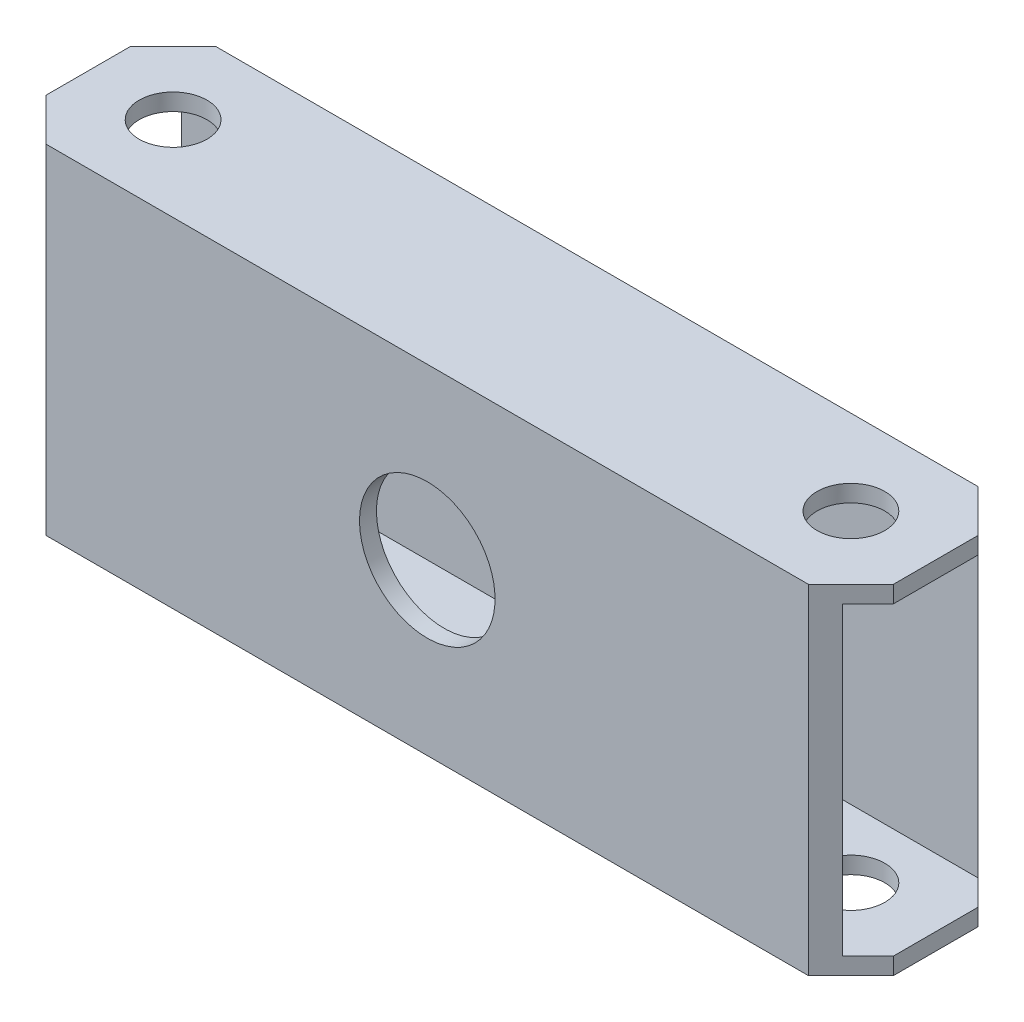
SolidWorks part; units mm, degrees
ref_plane "Front Plane" through (0, 0, 0) normal (0, 0, 1) x (1, 0, 0)
ref_plane "Top Plane" through (0, 0, 0) normal (0, 1, 0) x (1, 0, 0)
ref_plane "Right Plane" through (0, 0, 0) normal (1, 0, 0) x (0, 0, -1)
sketch "Sketch1" plane through (0, 0, 0) normal (0, 1, 0) x (1, 0, 0)
  line L1 (0, 0) -> (100, 0)
  line L2 (0, 0) -> (0, 20)
  line L3 (0, 20) -> (100, 20)
  line L4 (100, 0) -> (100, 20)
  dimension "D1" = 100
  dimension "D2" = 20
extrude "Boss-Extrude1" add sketch "Sketch1" along normal blind 40
sketch "Sketch2" plane through (0, 40, 0) normal (0, 1, 0) x (1, 0, 0)
  line L0 (50, 20) -> (50, 0)
  line L1 (100, 20) -> (0, 20) construction
  line L2 (0, 0) -> (100, 0) construction
  circle A0 centre (10, 10) radius 4
  circle A1 centre (90, 10) radius 4
extrude "Cut-Extrude1" cut sketch "Sketch2" against normal through all contours A0 | A1
sketch "Sketch3" plane through (0, 0, -20) normal (0, 0, -1) x (-1, 0, 0)
  line L0 (-100, 0) -> (0, 0) construction
  line L1 (0, 40) -> (0, 0) construction
  circle A0 centre (-50, 20) radius 8
  dimension "D1" = 16
  dimension "D2" = 20
  dimension "D3" = 50
extrude "Cut-Extrude2" cut sketch "Sketch3" against normal through all contours A0
sketch3d "3DSketch1"
  line L0 (100, 38, -18) -> (100, 38, -2)
  line L1 (100, 38, -2) -> (100, 2, -2)
  line L2 (100, 2, -2) -> (100, 2, -18)
  line L3 (100, 2, -18) -> (100, 38, -18)
  line L4 (100, 38, -18) -> (100, 38, -2)
  line L5 (100, 38, -2) -> (100, 2, -2)
  line L6 (100, 2, -2) -> (100, 2, -18)
  line L7 (100, 2, -18) -> (100, 38, -18)
  dimension "D1" = 2
extrude "Cut-Extrude3" cut sketch "3DSketch1" along direction (1, 0, 0) on the side of the normal through all contours L4 L5 L6 L7
chamfer "Chamfer1" distance 5 angle 45 4 edges at (100, 20, -20) (100, 20, 0) (0, 20, -20) (0, 20, 0)
